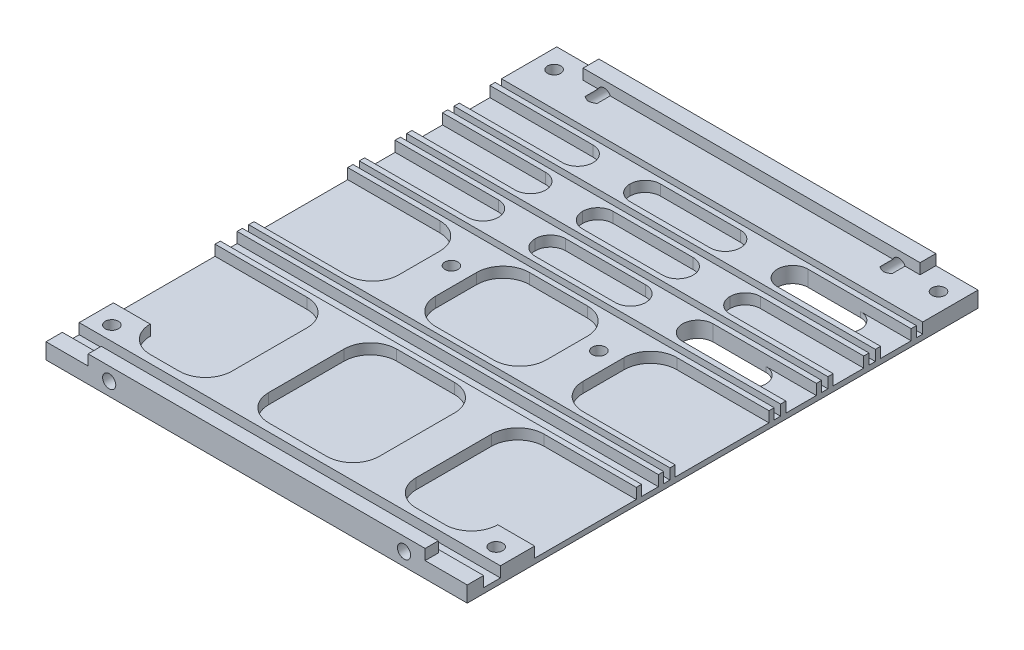
SolidWorks part; units mm, degrees
material "6061-T6 (SS)"
ref_plane "Front Plane" through (0, 0, 0) normal (0, 0, 1) x (1, 0, 0)
ref_plane "Top Plane" through (0, 0, 0) normal (0, 1, 0) x (1, 0, 0)
ref_plane "Right Plane" through (0, 0, 0) normal (1, 0, 0) x (0, 0, -1)
sketch "Sketch1" plane through (0, 0, 0) normal (0, 1, 0) x (1, 0, 0)
  line L0 (-28, 47) -> (28, 47) construction
  line L1 (-40, -48.5) -> (40, -48.5)
  line L2 (-40, -48.5) -> (-40, 48.5)
  line L3 (-40, 48.5) -> (40, 48.5)
  line L4 (40, -48.5) -> (40, 48.5)
  line L5 (-40, -48.5) -> (40, 48.5) construction
  line L6 (-40, 48.5) -> (40, -48.5) construction
  line L7 (28, 47) -> (28, -47) construction
  line L8 (28, -47) -> (-28, -47) construction
  line L9 (-28, -47) -> (-28, 47) construction
  line L10 (-40, 0) -> (-28, 0) construction
  line L12 (0, 47) -> (0, 48.5) construction
  circle A0 centre (-28, 47) radius 1.75
  circle A1 centre (28, 47) radius 1.75
  circle A2 centre (28, -47) radius 1.75
  circle A3 centre (-28, -47) radius 1.75
  point P0 (0, 0)
  dimension "D5" = 3.5
  dimension "D1" = 80
  dimension "D2" = 97
  dimension "D3" = 56
  dimension "D4" = 94
extrude "Boss-Extrude1" add sketch "Sketch1" along normal blind 1 contours L1 L4 L3 L2 A3 A2 A1 A0 | A0 | A1 | A2 | A3 | L2 L1 L4 L3 region at (0, 0, 0) region at (-28, 0, 46.9476) region at (-28, 0, -46.9476) region at (28, 0, 46.9476) region at (28, 0, -46.9476)
sketch "Sketch4" plane through (0, 1, 0) normal (0, 1, 0) x (1, 0, 0)
  line L1 (-40, 39) -> (40, 39)
  line L2 (-40, 39) -> (-40, 38)
  line L3 (-40, 38) -> (40, 38)
  line L4 (40, 39) -> (40, 38)
  line L6 (-40, 48.5) -> (40, 48.5) construction
  line L7 (-40, 36.8) -> (40, 36.8)
  line L8 (-40, 36.8) -> (-40, 35.8)
  line L9 (-40, 35.8) -> (40, 35.8)
  line L10 (40, 36.8) -> (40, 35.8)
  line L11 (-40, 38) -> (-40, 37.4) construction
  line L12 (-40, 37.4) -> (-40, 36.8) construction
  line L13 (-40, 37.4) -> (40, 37.4) construction
  line L14 (-28, 48.5) -> (-28, 37.4) construction
  line L15 (-40, -48.5) -> (-40, 48.5) construction
  line L16 (40, -48.5) -> (40, 48.5) construction
  dimension "D1" = 1
  dimension "D2" = 1.2
  dimension "D3" = 12
  dimension "D4" = 11.1
extrude "Boss-Extrude2" add sketch "Sketch4" along normal blind 2
pattern_linear "LPattern1" count 4 spacing 9 along (0, 0, 1) of "Boss-Extrude2"
ref_plane "Plane1" through (0, 0, -37.4) normal (0, 0, 1) x (1, 0, 0)
ref_plane "Plane2" through (0, 0, 0.1) normal (0, 0, 1) x (1, 0, 0)
mirror "Mirror1" about plane through (0, 0, 0.1) normal (0, 0, 1) of "LPattern1"
sketch "Sketch10" plane through (0, 1, 0) normal (0, 1, 0) x (1, 0, 0)
  line L0 (40, -39.2) -> (-40, -39.2) construction
  line L1 (-40, -18) -> (40, -18)
  line L2 (-40, -18) -> (-40, -39.2)
  line L3 (-40, -39.2) -> (40, -39.2)
  line L4 (40, -18) -> (40, -39.2)
  line L5 (40, -48.5) -> (40, -39.2) construction
extrude "Remove_3_rows" cut sketch "Sketch10" along normal through all
sketch "Sketch5" plane through (0, 1, 0) normal (0, -1, 0) x (1, 0, 0)
  line L0 (36.5, -44.5) -> (-36.5, -44.5) construction
  line L1 (-36.5, -44.5) -> (-36.5, 39.5) construction
  line L2 (-36.5, 39.5) -> (36.5, 39.5) construction
  line L3 (36.5, 39.5) -> (36.5, -44.5) construction
  line L4 (0, -44.5) -> (0, 0) construction
  line L5 (0, 0) -> (36.5, 0) construction
  line L6 (-36.5, -44.5) -> (-36.5, -48.5) construction
  line L7 (-40, -48.5) -> (40, -48.5) construction
  line L8 (-14, -2.5) -> (14, -2.5) construction
  line L9 (-14, -2.5) -> (-14, -44.5) construction
  line L10 (-14, -2.5) -> (-14, 39.5) construction
  point P3 (-36.5, 39.5)
  point P5 (36.5, 39.5)
  point P7 (36.5, -44.5)
  point P18 (-36.5, -44.5)
  point P20 (0, -2.5)
  point P24 (-14, -2.5)
  point P25 (14, -2.5)
  dimension "D1" = 28
  dimension "D2" = 73
  dimension "D3" = 84
  dimension "D4" = 4
sketch "Sketch12" plane through (0, 1, 0) normal (0, 1, 0) x (1, 0, 0)
  line L4 (-40, -13.8) -> (40, -13.8) construction
  line L5 (40, -13.8) -> (40, -43.8) construction
  line L6 (40, -43.8) -> (-40, -43.8) construction
  line L7 (-40, -12.2) -> (-40, -13.8) construction
  line L8 (-40, -11.2) -> (40, -11.2)
  line L9 (-40, -11.2) -> (-40, -12.2)
  line L10 (-40, -12.2) -> (40, -12.2)
  line L11 (40, -11.2) -> (40, -12.2)
  line L12 (40, -16.4) -> (-40, -16.4)
  line L13 (40, -16.4) -> (40, -15.4)
  line L14 (40, -15.4) -> (-40, -15.4)
  line L15 (-40, -16.4) -> (-40, -15.4)
  line L16 (-40, -13.8) -> (-40, -15.4) construction
  line L17 (-40, -42.2) -> (-40, -43.8) construction
  line L18 (-40, -40.7) -> (40, -40.7)
  line L19 (-40, -40.7) -> (-40, -42.2)
  line L20 (-40, -42.2) -> (40, -42.2)
  line L21 (40, -40.7) -> (40, -42.2)
  line L22 (40, -45.4) -> (-40, -45.4)
  line L23 (40, -45.4) -> (40, -46.9)
  line L24 (40, -46.9) -> (-40, -46.9)
  line L25 (-40, -45.4) -> (-40, -46.9)
  line L26 (-40, -43.8) -> (-40, -45.4) construction
  line L27 (-40, -11.2) -> (40, -11.2) construction
  line L28 (40, -48.5) -> (40, -12.2) construction
  line L30 (-40, -48.5) -> (-40, -12.2) construction
  dimension "D2" = 33.2
  dimension "D3" = 3.2
  dimension "D4" = 1
  dimension "D6" = 3.2
  dimension "D7" = 1.5
extrude "PayloadSlots" add sketch "Sketch12" along normal up to surface (2 mm away) up to face at (0, 3, 9.5)
sketch "Sketch16" plane through (0, 1, 0) normal (0, 1, 0) x (1, 0, 0)
  line L0 (-14, 2.5) -> (14, 2.5) construction
  line L1 (-14, 2.5) -> (14, 2.5)
  line L2 (-17.5, 2.5) -> (-17.5, -9)
  line L4 (-17.5, -9) -> (-10.5, -9)
  line L5 (-10.5, -9) -> (-10.5, 2.5)
  line L6 (10.5, 2.5) -> (10.5, -9)
  line L7 (10.5, -9) -> (17.5, -9)
  line L8 (17.5, -9) -> (17.5, 2.5)
  line L9 (-40, -9) -> (40, -9) construction
  circle A0 centre (-14, 2.5) radius 3.5
  circle A1 centre (14, 2.5) radius 3.5
  dimension "D1" = 7
  dimension "D2" = 7
extrude "Boss-Extrude8" add sketch "Sketch16" along normal up to surface (2 mm away) contours A0 | A0 L2 L5 | A1 L6 L8 | A1 region at (14, 1, -5.901) region at (14, 1, 4.5896) region at (-14, 1, 0.901) region at (-14, 1, 4.5896) up to face at (0, 3, 9.5)
sketch "Sketch22" plane through (0, 1, 0) normal (0, 1, 0) x (1, 0, 0)
  line L0 (-40, -48.5) -> (-40, -46.9) construction
  line L1 (-40, 48.5) -> (40, 48.5)
  line L2 (-40, 48.5) -> (-40, 39)
  line L3 (-40, 39) -> (40, 39)
  line L4 (40, 48.5) -> (40, 39)
  line L5 (40, -48.5) -> (-40, -48.5)
  line L6 (40, -48.5) -> (40, -46)
  line L7 (40, -46) -> (-40, -46)
  line L8 (-40, -48.5) -> (-40, -46)
  dimension "D1" = 2.5
extrude "Boss-Extrude9" add sketch "Sketch22" along normal blind 4
fillet "Fillet4" radius 5 4 edges at (-10.5, 2, 9) (-17.5, 2, 9) (10.5, 2, 9) (17.5, 2, 9)
sketch "Sketch23" plane through (0, 0, -48.5) normal (0, 0, -1) x (-1, 0, 0)
  line L0 (-28, 2.5) -> (28, 2.5) construction
  line L1 (28, 2.5) -> (40, 2.5) construction
  line L2 (-28, 2.5) -> (-40, 2.5) construction
  line L3 (40, 5) -> (40, 0) construction
  line L4 (-40, 5) -> (-40, 0) construction
  dimension "D1" = 2.5
  dimension "D2" = 56
ref_plane "Plane3" through (0, 0, 0) normal (0, 0, -1) x (-1, 0, 0)
hole_wizard "M3x0.5 Tapped Hole2" positions "Sketch24" profile "Sketch25" tap size "M3x0.5" standard "ANSI Metric"
sketch "Sketch24" plane through (0, 0, -48.5) normal (0, 0, -1) x (-1, 0, 0)
  point P0 (-28, 2.5)
  point P3 (28, 2.5)
sketch "Sketch25" plane through (28, 2.5, -48.5) normal (1, 0, 0) x (0, 1, 0)
  line L0 (0, 0) -> (0, 6.2511)
  line L1 (0, 6.2511) -> (1.25, 5.5)
  line L2 (1.25, 5.5) -> (1.25, 0)
  line L5 (1.25, 0) -> (0, 0)
  line L10 (0, 6.2511) -> (-1.25, 5.5) construction
  line L11 (0, -6.35) -> (0, 107.95) construction
  dimension "Tap Drill Dia." = 2.5
  dimension "Tap Drill Depth" = 5.5
  dimension "Drill Angle" = 118
cosmetic thread "Hole Thread7" parameters "D1"=5.1, "D2"=3
cosmetic thread "Hole Thread8" parameters "D1"=5.1, "D2"=3
mirror "Mirror2" about plane through (0, 0, 0) normal (0, 0, -1) of "M3x0.5 Tapped Hole2"
sketch "Sketch26" plane through (0, 5, 0) normal (0, 1, 0) x (1, 0, 0)
  line L0 (-40, 48.5) -> (-40, 39) construction
  line L1 (40, 39) -> (-40, 39)
  line L2 (40, 39) -> (40, 45.5)
  line L3 (40, 45.5) -> (-40, 45.5)
  line L4 (-40, 39) -> (-40, 45.5)
  line L5 (-28, 48.5) -> (-40, 48.5) construction
  line L6 (40, -48.5) -> (40, -46) construction
  line L7 (-40, -46) -> (40, -46)
  line L8 (-40, -46) -> (-40, -45.5)
  line L9 (-40, -45.5) -> (40, -45.5)
  line L10 (40, -46) -> (40, -45.5)
  line L11 (-40, -48.5) -> (40, -48.5) construction
  line L12 (40, 48.5) -> (-40, 48.5) construction
  line L13 (-40, -48.5) -> (-32, -48.5)
  line L14 (-40, -48.5) -> (-40, -45.5)
  line L15 (-40, -45.5) -> (-32, -45.5)
  line L16 (-32, -48.5) -> (-32, -45.5)
  line L17 (40, -48.5) -> (32, -48.5)
  line L18 (40, -48.5) -> (40, -45.5)
  line L19 (40, -45.5) -> (32, -45.5)
  line L20 (32, -48.5) -> (32, -45.5)
  line L21 (40, 45.5) -> (32, 45.5)
  line L22 (40, 45.5) -> (40, 48.5)
  line L23 (40, 48.5) -> (32, 48.5)
  line L24 (32, 45.5) -> (32, 48.5)
  line L25 (-32, 45.5) -> (-32, -45.5) construction
  line L26 (-40, 45.5) -> (-32, 45.5)
  line L27 (-40, 45.5) -> (-40, 48.5)
  line L28 (-40, 48.5) -> (-32, 48.5)
  line L29 (-32, 45.5) -> (-32, 48.5)
  line L30 (32, -45.5) -> (32, 45.5) construction
  line M16 (-40, 48.5) -> (-40, 39)
  line M17 (-40, 39) -> (40, 39)
  line M18 (40, 39) -> (40, 48.5)
  line M19 (40, 48.5) -> (-40, 48.5)
  dimension "D1" = 3
  dimension "D2" = 3
  dimension "D3" = 8
  dimension "D4" = 8
extrude "Cut-Extrude1" cut sketch "Sketch26" against normal up to surface (2 mm away) contours L10 L7 L8 L9 | L13 L16 L9 L14 | L20 L17 L18 L9 | L24 L3 M18 M19 | L3 M18 M16 M17 | L3 L29 M19 M16 region at (0, 5, -42.25) region at (36, 5, -47) region at (-36, 5, -47) region at (-36, 5, 47.25) region at (36, 5, 47.25) up to face at (0, 3, -38.5)
sketch "Sketch28" plane through (0, 1, 0) normal (0, 1, 0) x (1, 0, 0)
  line L0 (-40, 35.8) -> (40, 35.8) construction
  line L1 (-17.5, 35.8) -> (-10.5, 35.8)
  line L2 (-17.5, 35.8) -> (-17.5, -40.7)
  line L3 (-17.5, -40.7) -> (-10.5, -40.7)
  line L4 (-10.5, 35.8) -> (-10.5, -40.7)
  line L5 (40, -40.7) -> (-40, -40.7) construction
  line L6 (-40, -40.7) -> (-17.5, -40.7) construction
  line L7 (10.5, -40.7) -> (17.5, -40.7)
  line L8 (10.5, -40.7) -> (10.5, 35.8)
  line L9 (10.5, 35.8) -> (17.5, 35.8)
  line L10 (17.5, -40.7) -> (17.5, 35.8)
  line L11 (-10.5, -40.7) -> (10.5, -40.7) construction
  line L12 (40, -40.7) -> (17.5, -40.7) construction
  line L13 (-40, -16.4) -> (40, -16.4) construction
  line L14 (40, 21) -> (-40, 21) construction
  line L15 (40, 12) -> (-40, 12) construction
  line L16 (-40, 8.8) -> (40, 8.8) construction
  line L17 (-40, 17.8) -> (40, 17.8) construction
  line L18 (-40, 26.8) -> (40, 26.8) construction
  line L19 (40, 30) -> (-40, 30) construction
  line L20 (-40, -16.4) -> (40, -16.4)
  line L21 (40, 21) -> (-40, 21)
  line L22 (40, 12) -> (-40, 12)
  line L23 (-40, 8.8) -> (40, 8.8)
  line L24 (-40, 17.8) -> (40, 17.8)
  line L25 (-40, 26.8) -> (40, 26.8)
  line L26 (40, 30) -> (-40, 30)
  line L27 (-7.6, 14.9) -> (-7.6, 35.8) construction
  line L29 (7.6, 14.9) -> (7.6, 35.8) construction
  arc A0 (-10.5, 2.5) -> (-17.5, 2.5) centre (-14, 2.5) ccw construction
  arc A1 (-10.5, 2.5) -> (-17.5, 2.5) centre (-14, 2.5) ccw
  arc A2 (17.5, 2.5) -> (10.5, 2.5) centre (14, 2.5) ccw construction
  arc A3 (17.5, 2.5) -> (10.5, 2.5) centre (14, 2.5) ccw
  circle A4 centre (-7.6, 14.9) radius 2.9
  circle A5 centre (7.6, 14.9) radius 2.9
  circle A6 centre (-7.6, 27.8487) radius 2.9
  circle A7 centre (7.6, 27.8487) radius 2.9
  circle A8 centre (-7.6, 37.2035) radius 2.9
  circle A9 centre (7.6, 36.6874) radius 2.9
  circle A10 centre (-21.1091, 18.5) radius 3.6091
  circle A11 centre (-21.1091, 27.8487) radius 3.6091
  circle A12 centre (-22.4679, 37.2035) radius 4.9679
  line M13 (-40, -40.7) -> (40, -40.7)
  line M15 (40, -16.4) -> (-40, -16.4)
  dimension "D1" = 21
  dimension "D2" = 7
extrude "Boss-Extrude10" add sketch "Sketch28" along normal up to surface (2 mm away) contours L4 L2 M15 M13 | A1 L4 L23 L2 | L25 L8 L21 L10 | L26 L10 L9 L8 | L24 L2 L22 L4 | L25 L2 L21 L4 | L26 L4 L1 L2 | A3 L10 L23 L8 | L10 L8 M13 M15 | L24 L8 L22 L10 region at (-14, 1, -32.9) region at (-14, 1, -23.9) region at (-14, 1, -14.9) region at (14, 1, -23.9) region at (14, 1, -14.9) region at (14, 1, -32.9) region at (-14, 1, -6.9385) region at (14, 1, -6.9385) region at (-14, 1, 28.55) region at (14, 1, 28.55) up to face at (-0.0114, 3, -44.6318)
fillet "Fillet5" radius 5 12 edges at (-17.5, 2, -8.8) (10.5, 2, -8.8) (17.5, 2, -8.8) (-10.5, 2, -8.8) (17.5, 2, 16.4) (17.5, 2, 40.7) (-17.5, 2, 40.7) (10.5, 2, 40.7) (10.5, 2, 16.4) (-17.5, 2, 16.4) (-10.5, 2, 16.4) (-10.5, 2, 40.7)
fillet "Fillet6" radius 2.9 24 edges at (-10.5, 2, -17.8) (17.5, 2, -17.8) (17.5, 2, -26.8) (-10.5, 2, -26.8) (-10.5, 2, -35.8) (17.5, 2, -35.8) (17.5, 2, -30) (-10.5, 2, -30) (-10.5, 2, -21) (17.5, 2, -21) (17.5, 2, -12) (-10.5, 2, -12) (-17.5, 2, -12) (10.5, 2, -12) (-17.5, 2, -21) (10.5, 2, -21) (10.5, 2, -30) (10.5, 2, -17.8) (10.5, 2, -26.8) (10.5, 2, -35.8) (-17.5, 2, -17.8) (-17.5, 2, -26.8) (-17.5, 2, -35.8) (-17.5, 2, -30)
sketch "Sketch29" plane through (0, 1, 0) normal (0, 1, 0) x (1, 0, 0)
  line L0 (40, -40.7) -> (22.5, -40.7) construction
  line L1 (33, -40.7) -> (40, -40.7)
  line L2 (33, -40.7) -> (33, -35.7)
  line L3 (33, -35.7) -> (40, -35.7)
  line L4 (40, -40.7) -> (40, -35.7)
  line L5 (40, -40.7) -> (40, -16.4) construction
  line L6 (-33, -35.7) -> (33, -35.7) construction
  line L7 (-40, -40.7) -> (-33, -40.7)
  line L8 (-40, -40.7) -> (-40, -35.7)
  line L9 (-40, -35.7) -> (-33, -35.7)
  line L10 (-33, -40.7) -> (-33, -35.7)
  dimension "D1" = 5
  dimension "D2" = 7
extrude "Boss-Extrude11" add sketch "Sketch29" along normal up to surface (2 mm away) up to face at (0, 3, 28.55)
fillet "Fillet7" radius 5 2 edges at (33, 2, 40.7) (-33, 2, 40.7)
hole_wizard "M3x0.5 Tapped Hole1" positions "Sketch20" profile "Sketch21" tap size "M3x0.5" standard "ANSI Metric" end condition up to next
sketch "Sketch20" plane through (0, 0, 0) normal (0, -1, 0) x (-1, 0, 0)
  point P0 (36.5, 44.5)
  point P3 (-36.5, 44.5)
  point P6 (14, 2.5)
  point P9 (-14, 2.5)
  point P12 (36.5, -39.5)
  point P15 (-36.5, -39.5)
sketch "Sketch21" plane through (-36.5, 0, -44.5) normal (1, 0, 0) x (0, 0, -1)
  line L0 (0, 0) -> (0, 3)
  line L1 (0, 3) -> (1.25, 3)
  line L2 (1.25, 3) -> (1.25, 0)
  line L5 (1.25, 0) -> (0, 0)
  line L11 (0, -6.35) -> (0, 107.95) construction
  dimension "Thru Tap Drill Dia." = 2.5
  dimension "Thru Tap Drill Depth" = 3
cosmetic thread "Hole Thread1" parameters "D2"=3
cosmetic thread "Hole Thread2" parameters "D2"=3
cosmetic thread "Hole Thread3" parameters "D2"=3
cosmetic thread "Hole Thread4" parameters "D2"=3
cosmetic thread "Hole Thread5" parameters "D2"=3
cosmetic thread "Hole Thread6" parameters "D2"=3
sketch "Sketch30" plane through (0, 1, 0) normal (0, 1, 0) x (1, 0, 0)
  line L0 (20.4, 14.9) -> (30.4, 14.9) construction
  line L1 (20.4, 17.8) -> (30.4, 17.8)
  line L2 (20.4, 12) -> (30.4, 12)
  line L3 (20.4, 32.9) -> (30.4, 32.9) construction
  line L4 (20.4, 35.8) -> (30.4, 35.8)
  line L5 (20.4, 30) -> (30.4, 30)
  arc A2 (20.4, 17.8) -> (20.4, 12) centre (20.4, 14.9) ccw
  arc A3 (30.4, 12) -> (30.4, 17.8) centre (30.4, 14.9) ccw
  arc A4 (20.4, 35.8) -> (20.4, 30) centre (20.4, 32.9) ccw
  arc A5 (30.4, 30) -> (30.4, 35.8) centre (30.4, 32.9) ccw
  arc A6 (20.4, 35.8) -> (17.5, 32.9) centre (20.4, 32.9) ccw construction
  arc A7 (20.4, 17.8) -> (17.5, 14.9) centre (20.4, 14.9) ccw construction
  point P4 (25.4, 14.9)
  point P12 (25.4, 32.9)
  point P20 (0, 0)
  point P21 (20.4, 35.8)
  point P25 (20.4, 17.8)
  dimension "D1" = 10
  dimension "D2" = 10
extrude "Cut-Extrude2" cut sketch "Sketch30" against normal through all
